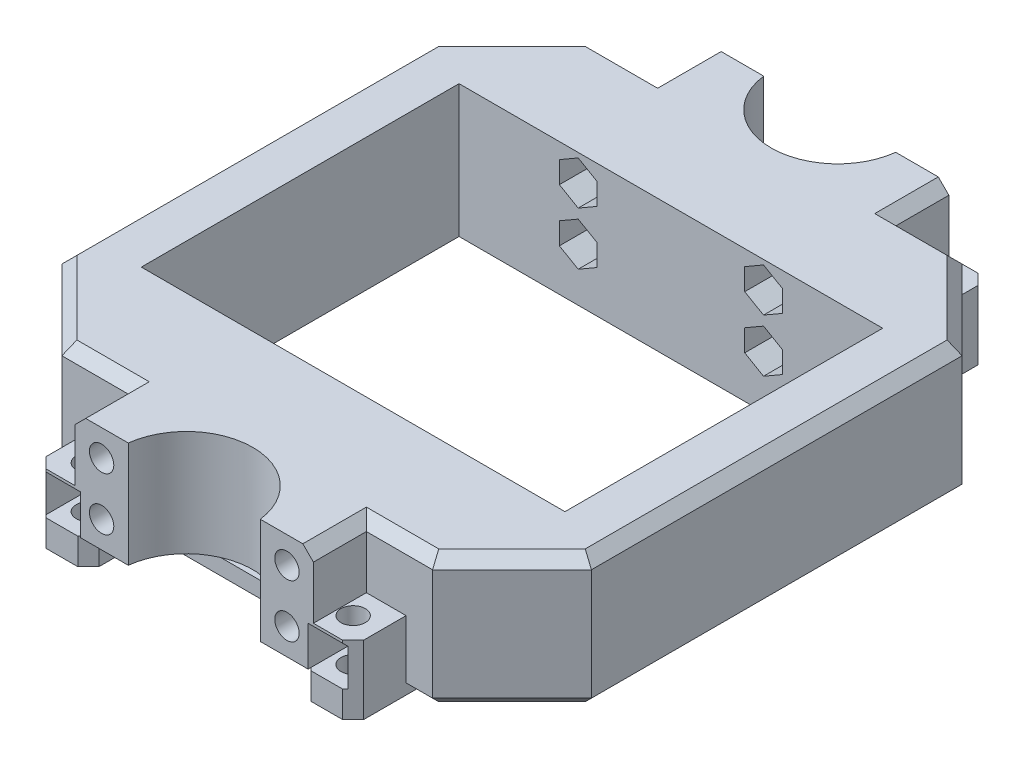
SolidWorks part; units mm, degrees
ref_plane "Front Plane" through (0, 0, 0) normal (0, 0, 1) x (1, 0, 0)
ref_plane "Top Plane" through (0, 0, 0) normal (0, 1, 0) x (1, 0, 0)
ref_plane "Right Plane" through (0, 0, 0) normal (1, 0, 0) x (0, 0, -1)
sketch "Sketch1" plane through (0, 0, 0) normal (0, 1, 0) x (1, 0, 0)
  line L0 (-50, 0) -> (50, 0)
  line L1 (-50, 0) -> (-50, 50)
  line L2 (50, 0) -> (50, 50)
  line L3 (-50, 50) -> (50, 50)
  point P4 (0, 0)
extrude "Boss-Extrude1" add sketch "Sketch1" along normal blind 25
chamfer "Chamfer1" distance 15 2 edges at (-50, 12.5, 0) (50, 12.5, 0)
ref_plane "Plane1" through (0, 25, 0) normal (0, 1, 0) x (1, 0, 0)
sketch "Sketch2" plane through (0, 25, 0) normal (0, 1, 0) x (1, 0, 0)
  line L0 (0, 0) -> (0, 20) construction
  line L1 (-40, 20) -> (40, 20)
  line L2 (-40, 20) -> (-50, 20) construction
  line L4 (-50, 50) -> (-50, 15) construction
  line L5 (40, 20) -> (50, 20) construction
  line L6 (50, 15) -> (50, 50) construction
  line L7 (-40, 20) -> (-40, 50)
  line L8 (50, 50) -> (-50, 50) construction
  line L9 (40, 20) -> (40, 50)
  line L10 (40, 50) -> (-40, 50)
  point P6 (0, 20)
  dimension "D1" = 20
  dimension "D2" = 10
extrude "Cut-Extrude1" cut sketch "Sketch2" against normal up to next
sketch "Sketch3" plane through (0, 25, 0) normal (0, 1, 0) x (1, 0, 0)
  line L0 (-20, 0) -> (20, 0) construction
  line L1 (-35, 0) -> (35, 0) construction
  line L2 (20, 0) -> (20, -10)
  line L3 (20, -10) -> (30, -10)
  line L4 (30, -10) -> (30, 0)
  line L5 (30, 0) -> (20, 0)
  line L6 (-20, 0) -> (-20, -10)
  line L7 (-20, -10) -> (-30, -10)
  line L8 (-30, -10) -> (-30, 0)
  line L9 (-30, 0) -> (-20, 0)
  circle A0 centre (-25, -5) radius 2.3
  circle A1 centre (25, -5) radius 2.3
  point P6 (0, 0)
  dimension "D5" = 4.6
  dimension "D6" = 4.6
  dimension "D1" = 10
  dimension "D2" = 10
  dimension "D3" = 40
  dimension "D4" = 10
extrude "Boss-Extrude3" add sketch "Sketch3" along normal blind 13 from surface starting at face at (0, 0, -27)
ref_plane "Plane2" through (0, 0, 10) normal (0, 0, 1) x (1, 0, 0)
sketch "Sketch4" plane through (0, 0, 10) normal (0, 0, 1) x (1, 0, 0)
  line L0 (25, 0) -> (25, 5) construction
  line L1 (30, 0) -> (20, 0) construction
  line L2 (21.5, 5) -> (28.5, 5)
  line L3 (28.5, 5) -> (28.5, 8.5)
  line L4 (28.5, 8.5) -> (21.5, 8.5)
  line L5 (21.5, 8.5) -> (21.5, 5)
  line L6 (-25, 0) -> (-25, 5) construction
  line L7 (-20, 0) -> (-30, 0) construction
  line L8 (-28.5, 5) -> (-21.5, 5)
  line L9 (-21.5, 5) -> (-21.5, 8.5)
  line L10 (-21.5, 8.5) -> (-28.5, 8.5)
  line L11 (-28.5, 8.5) -> (-28.5, 5)
  point P7 (25, 5)
  point P16 (-25, 5)
  dimension "D1" = 5
  dimension "D2" = 7
  dimension "D3" = 3.5
  dimension "D4" = 7
extrude "Cut-Extrude2" cut sketch "Sketch4" against normal blind 9
chamfer "Chamfer2" distance 4 2 edges at (25, 8.5, 10) (-25, 8.5, 10)
ref_plane "Plane3" through (0, 0, -50) normal (0, 0, -1) x (-1, 0, 0)
sketch "Sketch7" plane through (0, 0, -50) normal (0, 0, -1) x (-1, 0, 0)
  line L0 (45, 0) -> (45, 5) construction
  line L1 (40, 0) -> (50, 0) construction
  line L2 (45, 25) -> (45, 20) construction
  line L3 (40, 25) -> (50, 25) construction
  line L4 (47.5, 5) -> (42.5, 5)
  line L5 (42.5, 5) -> (42.5, 10)
  line L6 (42.5, 10) -> (47.5, 10)
  line L7 (47.5, 10) -> (47.5, 5)
  line L8 (47.5, 20) -> (42.5, 20)
  line L9 (42.5, 20) -> (42.5, 15)
  line L10 (42.5, 15) -> (47.5, 15)
  line L11 (47.5, 15) -> (47.5, 20)
  point P11 (45, 5)
  point P16 (45, 20)
  dimension "D2" = 5
  dimension "D4" = 5
  dimension "D1" = 5
  dimension "D3" = 5
  dimension "D5" = 5
  dimension "D6" = 5
sketch "Sketch8" plane through (0, 0, -50) normal (0, 0, -1) x (-1, 0, 0)
  line L0 (-45, 25) -> (-45, 20) construction
  line L1 (-50, 25) -> (-40, 25) construction
  line L2 (-45, 0) -> (-45, 5) construction
  line L3 (-50, 0) -> (-40, 0) construction
  line L4 (-47.5, 20) -> (-42.5, 20)
  line L5 (-42.5, 20) -> (-42.5, 15)
  line L6 (-42.5, 15) -> (-47.5, 15)
  line L7 (-47.5, 15) -> (-47.5, 20)
  line L8 (-47.5, 5) -> (-42.5, 5)
  line L9 (-42.5, 5) -> (-42.5, 10)
  line L10 (-42.5, 10) -> (-47.5, 10)
  line L11 (-47.5, 10) -> (-47.5, 5)
  point P11 (-45, 20)
  point P16 (-45, 5)
  dimension "D3" = 5
  dimension "D4" = 5
  dimension "D1" = 5
  dimension "D2" = 5
  dimension "D5" = 5
  dimension "D6" = 5
sketch "Sketch9" plane through (0, 0, 10) normal (0, 0, 1) x (1, 0, 0)
  line L0 (-22.5, 25) -> (22.5, 25)
  line L1 (-35, 25) -> (35, 25) construction
  line L2 (22.5, 25) -> (22.5, 5)
  line L3 (22.5, 5) -> (-22.5, 5)
  line L4 (-22.5, 5) -> (-22.5, 25)
  line L5 (0, 0) -> (0, 25.0197) construction
  point P5 (0, 25.0197)
  dimension "D1" = 45
  dimension "D2" = 20
  dimension "D3" = 22.5
extrude "Boss-Extrude4" add sketch "Sketch9" against normal blind 10
extrude "Cut-Extrude3" cut sketch "Sketch4<2>" against normal blind 10
sketch "Sketch4<2>" plane through (0, 0, 10) normal (0, 0, 1) x (1, 0, 0) same geometry as "Sketch4"
chamfer "Chamfer3" distance 4 2 edges at (-22, 8.5, 10) (22, 8.5, 10)
ref_plane "Plane4" through (0, 25, 0) normal (0, 1, 0) x (1, 0, 0)
sketch "Sketch10" plane through (0, 25, 0) normal (0, 1, 0) x (1, 0, 0)
  line L0 (0, 0) -> (0, -10) construction
  line L1 (22.5, -10) -> (-22.5, -10) construction
  line L2 (0, -10) -> (0, -11.5) construction
  circle A0 centre (0, -11.5) radius 12.55
  dimension "D2" = 25.1
  dimension "D1" = 1.5
extrude "Cut-Extrude4" cut sketch "Sketch10" against normal blind 20
ref_plane "Plane5" through (0, 0, 10) normal (0, 0, 1) x (1, 0, 0)
sketch "Sketch11" plane through (0, 0, 10) normal (0, 0, 1) x (1, 0, 0)
  line L0 (0, 0) -> (0, 15) construction
  line L1 (0, 15) -> (-17.5, 15) construction
  line L2 (-17.5, 10) -> (-17.5, 20) construction
  circle A0 centre (-17.5, 20) radius 2.3
  circle A1 centre (-17.5, 10) radius 2.3
  point P7 (-17.5, 15)
  dimension "D4" = 4.6
  dimension "D5" = 4.6
  dimension "D1" = 15
  dimension "D2" = 17.5
  dimension "D3" = 10
extrude "Cut-Extrude5" cut sketch "Sketch11" against normal up to next
mirror "Mirror1" about plane through (0, 0, 0) normal (1, 0, 0) of "Cut-Extrude5"
sketch "Sketch12" plane through (0, 0, 10) normal (0, 0, 1) x (1, 0, 0)
  line L1 (-13.95, 22.0496) -> (-17.5, 24.0992)
  line L2 (-17.5, 24.0992) -> (-21.05, 22.0496)
  line L3 (-21.05, 22.0496) -> (-21.05, 17.9504)
  line L4 (-21.05, 17.9504) -> (-17.5, 15.9008)
  line L5 (-17.5, 15.9008) -> (-13.95, 17.9504)
  line L6 (-13.95, 17.9504) -> (-13.95, 22.0496)
  line L7 (-13.95, 12.0496) -> (-17.5, 14.0992)
  line L8 (-17.5, 14.0992) -> (-21.05, 12.0496)
  line L9 (-21.05, 12.0496) -> (-21.05, 7.9504)
  line L10 (-21.05, 7.9504) -> (-17.5, 5.9008)
  line L11 (-17.5, 5.9008) -> (-13.95, 7.9504)
  line L12 (-13.95, 7.9504) -> (-13.95, 12.0496)
  circle A0 centre (-17.5, 20) radius 3.55 construction
  circle A1 centre (-17.5, 10) radius 3.55 construction
  dimension "D1" = 7.1
  dimension "D2" = 7.1
extrude "Cut-Extrude6" cut sketch "Sketch12" against normal up to next from offset 10 offset against normal yes
mirror "Mirror2" about plane through (0, 0, 0) normal (1, 0, 0) of "Cut-Extrude6"
chamfer "Chamfer4" distance 2 19 edges at (0, 0, 0) (-32.5, 0, 0) (-50, 0, -32.5) (-42.5, 0, -7.5) (-50, 25, -32.5) (-42.5, 25, -7.5) (-28.75, 25, 0) (-22.5, 25, 5) (-30, 6.5, 10) (-20, 2.5, 10) (20, 2.5, 10) (30, 6.5, 10) (32.5, 0, 0) (42.5, 0, -7.5) (50, 0, -32.5) (50, 25, -32.5) (42.5, 25, -7.5) (22.5, 25, 5) (28.75, 25, 0)
sketch "Sketch13" plane through (0, 0, 0) normal (0, 1, 0) x (1, 0, 0)
  line L0 (0, 0) -> (0, 10) construction
  line L1 (-20, 10) -> (20, 10)
  line L2 (-20, 10) -> (-20, 15)
  line L3 (-20, 15) -> (20, 15)
  line L4 (20, 15) -> (20, 10)
  point P5 (0, 10)
  dimension "D1" = 10
  dimension "D2" = 40
  dimension "D3" = 5
extrude "Cut-Extrude7" cut sketch "Sketch13" along normal blind 5
chamfer "Chamfer5" distance 4.75 1 edges at (0, 5, -15)
mirror "Mirror3" about plane through (0, 0, -50) normal (0, 0, -1) of bodies 121
